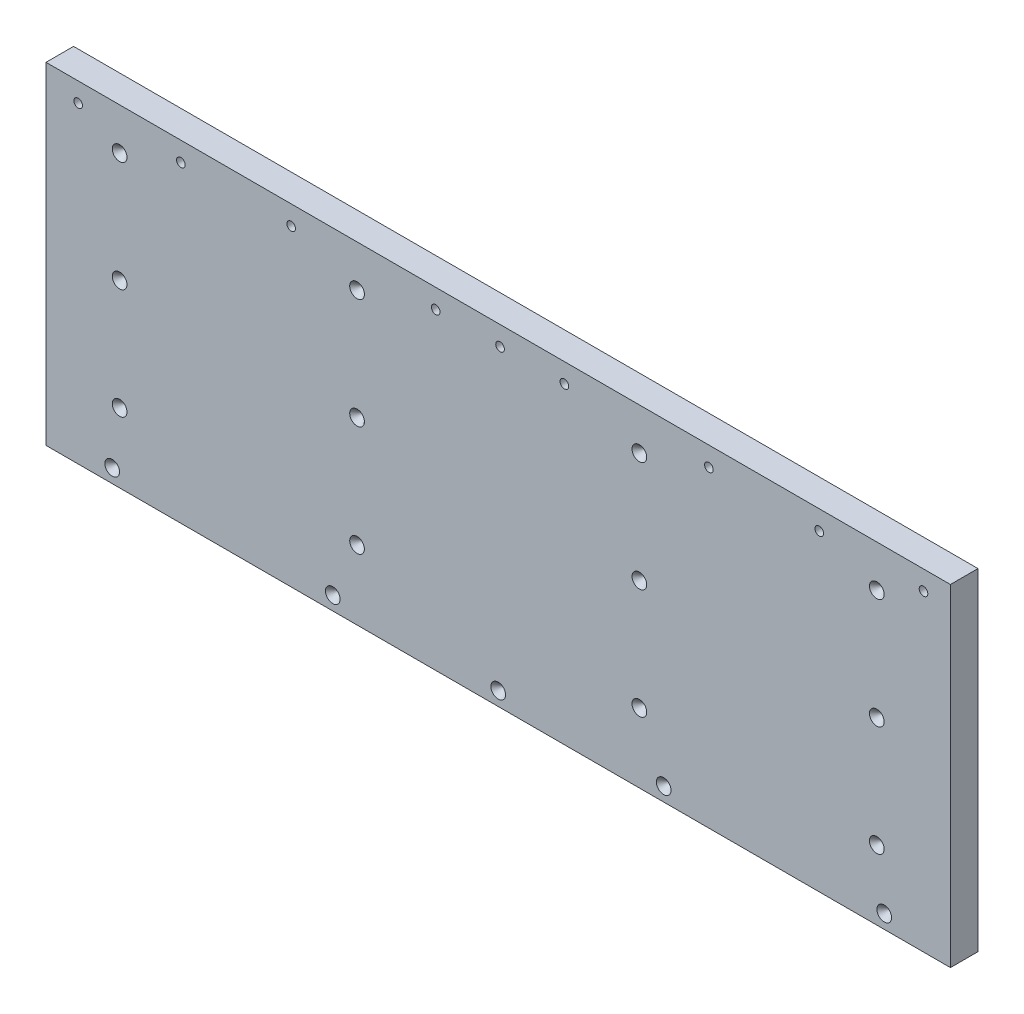
SolidWorks part; units mm, degrees
material "MDF"
ref_plane "Front Plane" through (0, 0, 0) normal (0, 0, 1) x (1, 0, 0)
ref_plane "Top Plane" through (0, 0, 0) normal (0, 1, 0) x (1, 0, 0)
ref_plane "Right Plane" through (0, 0, 0) normal (1, 0, 0) x (0, 0, -1)
sketch "Sketch1" plane through (0, 0, 0) normal (0, 0, 1) x (1, 0, 0)
  line L0 (128.7463, -697.8385) -> (128.7463, -132.715) construction
  line L1 (-496.0937, -132.715) -> (128.7463, -132.715)
  line L2 (-496.0937, -132.715) -> (-496.0937, -361.95)
  line L3 (-496.0937, -361.95) -> (128.7463, -361.95)
  line L4 (128.7463, -132.715) -> (128.7463, -361.95)
  line L5 (-496.0937, -132.715) -> (-496.0937, -697.8385) construction
  line L12 (128.7463, -132.715) -> (-84.6137, -132.715) construction
  line L13 (-290.722, -342.9) -> (-271.672, -342.9) construction
  dimension "D1" = 19.05
extrude "Boss-Extrude1" add sketch "Sketch1" along normal blind 19.05
hole_wizard "5/64 (0.07813) Diameter Hole1" positions "Sketch5" profile "Sketch6" hole size "5/64" standard "ANSI Inch"
sketch "Sketch5" plane through (-182.4037, -6471.4599, 19.05) normal (0, 0, 1) x (1, 0, 0)
  line L1 (-1.27, 6109.5099) -> (-1.27, 6338.7449) construction
  point P0 (-262.8265, 6157.4524)
  point P6 (-98.7933, 6157.4524)
  point P18 (-262.8265, 6233.6524)
  point P19 (-98.7933, 6233.6524)
  point P22 (-262.8265, 6309.8524)
  point P23 (-98.7933, 6309.8524)
  point P24 (-267.97, 6119.0349)
  point P34 (-115.57, 6119.0349)
  point P37 (-1.27, 6119.0349)
  point P40 (113.03, 6119.0349)
  point P44 (265.43, 6119.0349)
  point P55 (96.2533, 6309.8524)
  point P56 (260.2865, 6309.8524)
  point P59 (96.2533, 6233.6524)
  point P60 (260.2865, 6233.6524)
  point P63 (96.2533, 6157.4524)
  point P64 (260.2865, 6157.4524)
sketch "Sketch6" plane through (-445.2302, -314.0075, 19.05) normal (1, 0, 0) x (0, -1, 0)
  line L0 (0, 0) -> (0, 38.6962)
  line L1 (0, 38.6962) -> (0.9923, 38.1)
  line L2 (0.9923, 38.1) -> (0.9923, 4.7024)
  line L3 (0.9923, 4.7024) -> (5.08, 0)
  line L4 (5.08, 0) -> (0, 0)
  line L5 (-0.9923, 4.7024) -> (-5.08, 0) construction
  line L6 (0, 38.6962) -> (-0.9923, 38.1) construction
  line L7 (0, -6.35) -> (0, 107.95) construction
  dimension "Hole Dia." = 1.9845
  dimension "Hole Depth" = 38.1
  dimension "Near C'Sink Dia." = 10.16
  dimension "Near C'Sink Angle" = 82
  dimension "Drill Angle" = 118
hole_wizard "15/64 (0.23438) Diameter Hole1" positions "Sketch7" profile "Sketch8" hole size "15/64" standard "ANSI Inch" end condition up to next
sketch "Sketch7" plane through (0, 0, 0) normal (0, 0, -1) x (-1, 0, 0)
  point P0 (402.9075, -146.05)
  point P2 (326.7075, -146.05)
  point P4 (226.8537, -146.05)
  point P6 (182.4037, -146.05)
  point P8 (137.9537, -146.05)
  point P10 (38.1, -146.05)
  point P12 (-38.1, -146.05)
  point P13 (473.8687, -146.05)
  point P17 (-110.1471, -146.05)
sketch "Sketch8" plane through (-402.9075, -146.05, 0) normal (1, 0, 0) x (0, 1, 0)
  line L0 (0, 0) -> (0, 19.05)
  line L1 (0, 19.05) -> (2.9766, 19.05)
  line L2 (2.9766, 19.05) -> (2.9766, 0)
  line L5 (2.9766, 0) -> (0, 0)
  line L11 (0, -6.35) -> (0, 107.95) construction
  dimension "Thru Hole Dia." = 5.9533
  dimension "Thru Hole Depth" = 19.05
